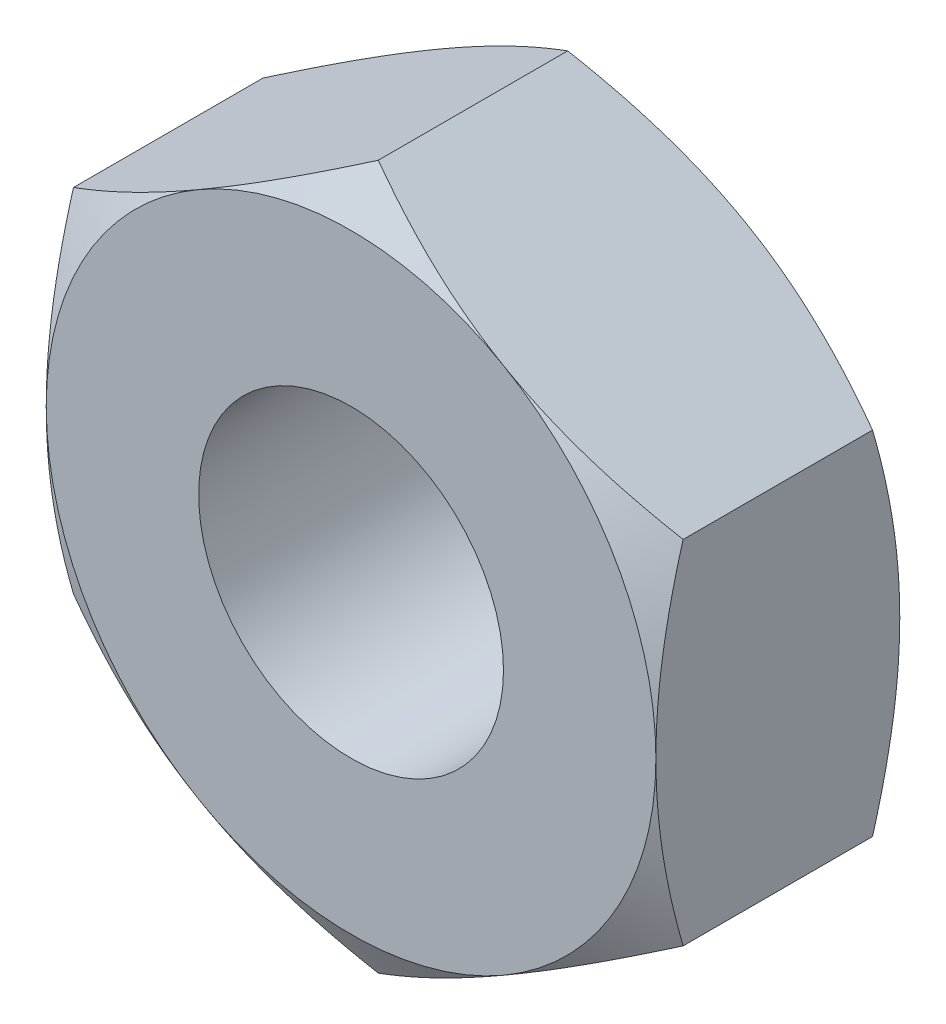
SolidWorks part; units mm, degrees
ref_plane "Front Plane" through (0, 0, 0) normal (0, 0, 1) x (1, 0, 0)
ref_plane "Top Plane" through (0, 0, 0) normal (0, 1, 0) x (1, 0, 0)
ref_plane "Right Plane" through (0, 0, 0) normal (1, 0, 0) x (0, 0, -1)
sketch "Sketch1" plane through (0, 0, 0) normal (1, 0, 0) x (0, 0, -1)
  line L0 (-1, 0) -> (1, 0) construction
  line L1 (-1, -2.5) -> (-1, 2.5) construction
  line L2 (1, -2.5) -> (1, 2.5) construction
  line L3 (-1, -1.25) -> (-1, 1.25) construction
  line L4 (-1.4219, 1.2987) -> (-1.1969, 0.909) construction
  line L5 (-1.1969, 0.909) -> (-0.9719, 1.2987) construction
  line L6 (-0.9719, 1.2987) -> (-1.4219, 1.2987) construction
  line L7 (-1.4078, 1.2744) -> (-0.9859, 1.2744) construction
  line L8 (-1.3938, 1.25) -> (-1, 1.25) construction
  line L9 (-1.225, 0.9577) -> (-1.1688, 0.9577) construction
  line L10 (-1.1969, 0.9577) -> (-1.1969, 0.909) construction
  line L11 (-1.1969, 1.2987) -> (-1.1969, 1.25) construction
  point P4 (0, 0)
  point P7 (-1, 0)
  point P11 (1, 0)
  point P14 (-1, 0)
  point P26 (-1.1969, 1.2744)
  point P27 (-1, -1.25)
  dimension "Height" = 2
  dimension "Width" = 5
  dimension "Thread OD" = 2.5
  dimension "D1" = 60
  dimension "Pitch" = 0.45
  dimension "D2" = 0.0562
sketch "Sketch2" plane through (0, 0, 0) normal (0, 0, 1) x (1, 0, 0)
  line L1 (0, 2.8868) -> (-2.5, 1.4434)
  line L2 (-2.5, 1.4434) -> (-2.5, -1.4434)
  line L3 (-2.5, -1.4434) -> (0, -2.8868)
  line L4 (0, -2.8868) -> (2.5, -1.4434)
  line L5 (2.5, -1.4434) -> (2.5, 1.4434)
  line L6 (2.5, 1.4434) -> (0, 2.8868)
  circle A0 centre (0, 0) radius 2.5 construction
  circle A1 centre (0, 0) radius 1.25
extrude "Boss-Extrude1" add sketch "Sketch2" along normal up to vertex (1 mm away) and the other way up to vertex (1 mm away) up to point (0, -2.5, 1) other way up to point (0, -2.5, -1)
sketch "Sketch3" plane through (0, 0, 1) normal (0, 0, 1) x (1, 0, 0)
  circle A0 centre (0, 0) radius 2.5
extrude "Cut-Extrude1" cut sketch "Sketch3" against normal through all draft 60 flip side to cut
mirror "Mirror1" about plane through (0, 0, 0) normal (0, 0, 1) of "Cut-Extrude1"
ref_axis "Center Axis 1" through (0, 0, -10.9016) along (0, 0, 1)
ref_plane "Contact Plane 1" through (0, 0, 1) normal (0, 0, 1) x (1, 0, 0)
ref_plane "Contact Plane 2" through (0, 0, -1) normal (0, 0, -1) x (-1, 0, 0)
sketch "Sketch4" [suppressed] plane through (0, 0, 0) normal (1, 0, 0) x (0, 0, -1)
  line L1 (-1.4078, 1.2744) -> (-1.225, 0.9577)
  line L2 (-1.225, 0.9577) -> (-1.1688, 0.9577)
  line L3 (-1.1688, 0.9577) -> (-0.9859, 1.2744)
  line L4 (-1.4078, 1.2744) -> (-0.9859, 1.2744) construction
  line L5 (-1.4078, 1.2744) -> (-0.9859, 1.2744)
sketch "Sketch5" [suppressed] plane through (0, 0, 1) normal (0, 0, 1) x (1, 0, 0)
  circle A0 centre (0, 0) radius 1.25 construction
  circle A1 centre (0, 0) radius 1.25
curve "Helix/Spiral1" [suppressed] pitch 0.45 height 2.45 turns 5.4444
sweep "Sweep1" [suppressed] add profiles "Sketch4" path "Helix/Spiral1"
sketch "Sketch6" [suppressed] plane through (0, 0, 1) normal (0, 0, 1) x (1, 0, 0)
  circle A1 centre (0, 0) radius 1.2744
extrude "Cut-Extrude2" [suppressed] cut sketch "Sketch6" along normal through all and the other way through all draft 45
sketch "Sketch7" [suppressed] plane through (0, 0, -1) normal (0, 0, -1) x (-1, 0, 0)
  circle A1 centre (0, 0) radius 1.2744
  circle A2 centre (0, 0) radius 1.2744
  dimension "D1" = 0
extrude "Cut-Extrude3" [suppressed] cut sketch "Sketch7" along normal through all and the other way through all draft 45
equation "\"D2@Sketch1\"=\"Pitch@Sketch1\"/8"
equation "\"D4@Helix/Spiral1\"=\"Pitch@Sketch1\""
equation "\"D3@Helix/Spiral1\"=\"Height@Sketch1\"+\"Pitch@Sketch1\""
